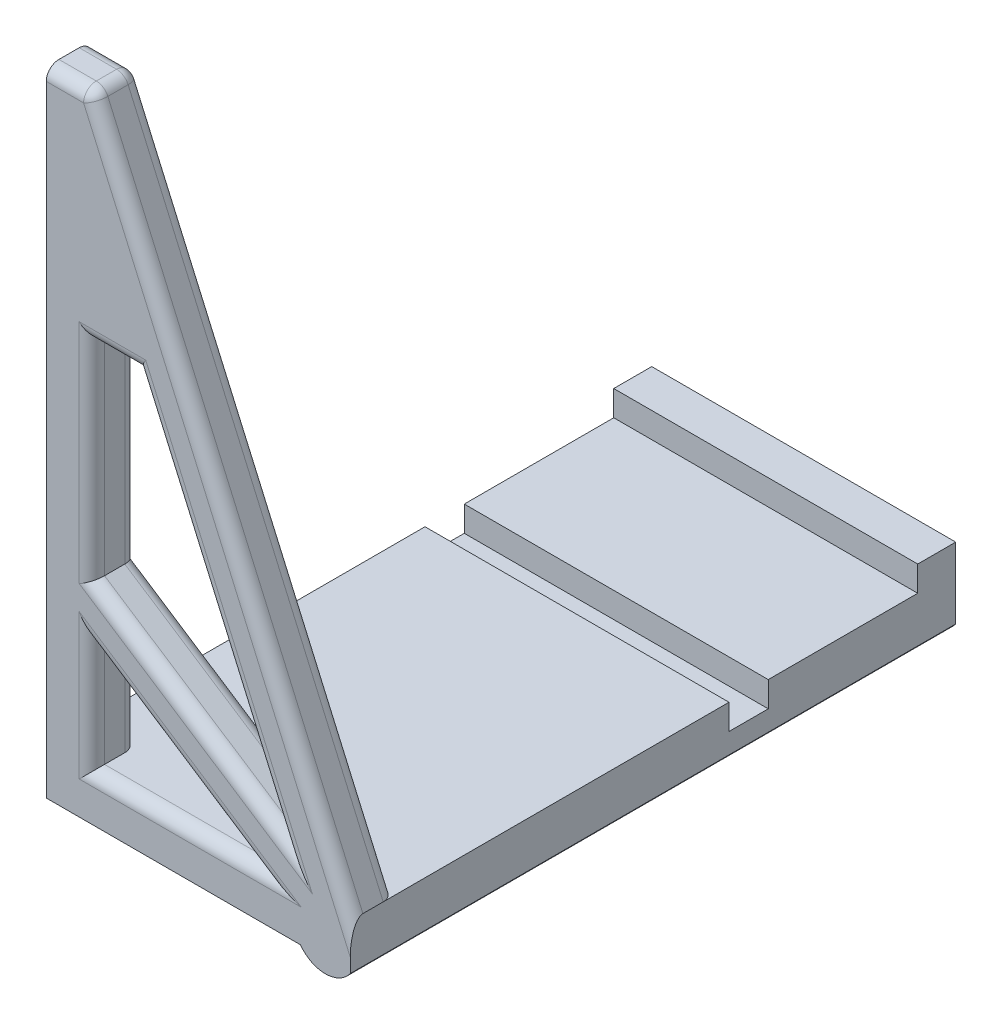
SolidWorks part; units mm, degrees
ref_plane "前基準面" through (0, 0, 0) normal (0, 0, 1) x (1, 0, 0)
ref_plane "上基準面" through (0, 0, 0) normal (0, 1, 0) x (1, 0, 0)
ref_plane "右基準面" through (0, 0, 0) normal (1, 0, 0) x (0, 0, -1)
sketch "草圖1" plane through (0, 0, 0) normal (1, 0, 0) x (0, 0, -1)
  line L0 (-179.6667, 241.3333) -> (-179.6667, -8.6667)
  line L1 (-179.6667, -8.6667) -> (59.3333, -8.6667)
  line L2 (59.3333, -8.6667) -> (59.3333, 9.3333)
  line L3 (44.3333, 9.3333) -> (-161.6667, 9.3333)
  line L4 (-161.6667, 9.3333) -> (-161.6667, 241.3333)
  line L5 (-161.6667, 241.3333) -> (-179.6667, 241.3333)
  line L8 (59.3333, 9.3333) -> (59.3333, 19.3333)
  line L9 (59.3333, 19.3333) -> (44.3333, 19.3333)
  line L10 (44.3333, 9.3333) -> (44.3333, 19.3333)
  dimension "D1" = 250
  dimension "D2" = 239
  dimension "D3" = 18
  dimension "D4" = 18
  dimension "D5" = 10
  dimension "D6" = 15
  dimension "D7" = 18
extrude "填料-伸長1" add sketch "草圖1" along normal blind 120
sketch "草圖2" plane through (120, 0, 0) normal (1, 0, 0) x (0, 0, -1)
  line L0 (-30.1667, 9.3333) -> (-30.1667, -0.6667)
  line L1 (-30.1667, -0.6667) -> (-14.6667, -0.6667)
  line L2 (-14.6667, -0.6667) -> (-14.6667, 9.3333)
  line L3 (-14.6667, 9.3333) -> (-30.1667, 9.3333)
  line L4 (44.3333, 9.3333) -> (-161.6667, 9.3333) construction
  line L5 (59.3333, -8.6667) -> (59.3333, 19.3333) construction
  dimension "D1" = 15.5
  dimension "D2" = 10
  dimension "D3" = 0
  dimension "D4" = 74
extrude "除料-伸長1" cut sketch "草圖2" against normal through all
sketch "草圖3" plane through (0, 0, 179.6667) normal (0, 0, 1) x (1, 0, 0)
  line L0 (120, -8.6667) -> (120, 9.3333)
  line L1 (120, 241.3333) -> (120, -8.6667) construction
  dimension "D1" = 18
sketch "草圖4" plane through (0, 0, 179.6667) normal (0, 0, 1) x (1, 0, 0)
  line L0 (0, 241.3333) -> (18, 241.3333)
  line L1 (120, 241.3333) -> (0, 241.3333) construction
  line L2 (18, 241.3333) -> (120, 9.3333)
  line L3 (120, 9.3333) -> (120, 241.3333)
  line L4 (120, 241.3333) -> (18, 241.3333)
  line M3 (120, -8.6667) -> (120, 241.3333)
  line M4 (120, 241.3333) -> (0, 241.3333)
  dimension "D1" = 18
extrude "除料-伸長2" cut sketch "草圖4" against normal blind 40 contours L2 M4 M3 region at (86, 164, 179.6667)
sketch "草圖5" plane through (0, 0, 179.6667) normal (0, 0, 1) x (1, 0, 0)
  line L0 (36, 155.6688) -> (100.3371, 9.3333)
  line L1 (18, 241.3333) -> (120, 9.3333) construction
  line L2 (18, 155.6688) -> (18, 9.3333)
  line L3 (0, 241.3333) -> (0, -8.6667) construction
  line L4 (18, 9.3333) -> (100.3371, 9.3333)
  line L5 (120, -8.6667) -> (0, -8.6667) construction
  line L6 (18, 155.6688) -> (36, 155.6688)
  dimension "D1" = 18
  dimension "D2" = 18
  dimension "D3" = 18
  dimension "D4" = 18
extrude "除料-伸長3" cut sketch "草圖5" against normal blind 40
fillet "圓角16" radius 5 5 edges at (69, 125.3333, 161.6667) (69, 125.3333, 179.6667) (9, 241.3333, 161.6667) (18, 241.3333, 170.6667) (9, 241.3333, 179.6667)
sketch "草圖8" plane through (0, 0, 179.6667) normal (0, 0, 1) x (1, 0, 0)
  line L0 (120, -8.6667) -> (100.34, -8.6667)
  line L1 (120, -8.6667) -> (0, -8.6667) construction
  line L2 (100.34, -8.6667) -> (100.34, -3.6667)
  line L3 (100.34, -3.6667) -> (120, -3.6667)
  line L4 (100.34, -8.6667) -> (120, -8.6667)
  line L5 (120, -3.6667) -> (120, -8.6667)
  line L6 (100.3371, 9.3333) -> (120, 9.3333)
  line L7 (120, 9.3333) -> (120, -8.6667)
  line L8 (110.17, -8.6667) -> (110.17, -13.6667) construction
  arc A0 (120, -8.6667) -> (100.34, -8.6667) centre (110.17, -1.5038) cw
  line M9 (0, -8.6667) -> (120, -8.6667)
  dimension "D4" = 5
  dimension "D1" = 19.66
  dimension "D2" = 5
  dimension "D3" = 19.66
extrude "填料-伸長2" add sketch "草圖8" against normal blind 239 contours L8 A0 M9 | L4 L8 A0 region at (113.9836, -10.7067, 179.6667) region at (106.3564, -10.7067, 179.6667)
sketch "草圖9" plane through (0, 0, 179.6667) normal (0, 0, 1) x (1, 0, 0)
  line L0 (83.8721, 9.3333) -> (100.3371, 9.3333)
  line L1 (100.3371, 9.3333) -> (93.7099, 24.4071)
  line L3 (18, 73.8277) -> (18, 52.3322)
  line L4 (100.3371, 9.3333) -> (18, 63.0799) construction
  line L5 (18, 63.0799) -> (13.0805, 55.5435)
  line L6 (105.2567, 16.8698) -> (95.4176, 1.7969)
  line L7 (13.0805, 55.5435) -> (95.4176, 1.7969)
  line L8 (22.9195, 70.6164) -> (105.2567, 16.8698)
  line L9 (93.7112, 24.4063) -> (100.3371, 9.3333)
  line L10 (18, 63.0799) -> (10.4635, 67.9995)
  line L11 (10.4635, 67.9995) -> (15.3831, 75.5359)
  line L12 (15.3831, 75.5359) -> (22.9195, 70.6164)
  line M11 (18, 9.3333) -> (18, 155.6688)
  line M13 (36, 155.6688) -> (100.3371, 9.3333)
  line M14 (100.3371, 9.3333) -> (18, 9.3333)
  dimension "D1" = 33.135
  dimension "D2" = 9
  dimension "D3" = 90
  dimension "D4" = 90
  dimension "D5" = 9
  dimension "D6" = 9
  dimension "D7" = 9
  dimension "D8" = 90
extrude "填料-伸長3" add sketch "草圖9" against normal blind 18 contours L4 L8 L12 L3 M13 | L4 L7 M14 M11 | L7 L6 M14 | L8 L9 L6 | L12 L11 L10 L3 | L5 L7 M11 | L5 L7 L6 L8 L12 L11 L10 region at (55.2047, 33.6192, 179.6667) region at (93.209, 6.8212, 179.6667) region at (57.5349, 42.5718, 179.6667) region at (99.7683, 16.8698, 179.6667) region at (16.3602, 56.9852, 179.6667) region at (15.263, 69.3725, 179.6667)
fillet "圓角17" radius 5 13 edges at (27, 155.6688, 179.6667) (27, 155.6688, 161.6667) (64.8549, 90.0379, 161.6667) (50.9361, 30.8328, 161.6667) (18, 30.8328, 161.6667) (18, 114.7482, 161.6667) (18, 114.7482, 179.6667) (64.8549, 90.0379, 179.6667) (55.8549, 49.1174, 161.6667) (55.8549, 49.1174, 179.6667) (18, 30.8328, 179.6667) (50.9361, 30.8328, 179.6667) (50.9361, 9.3333, 179.6667)
